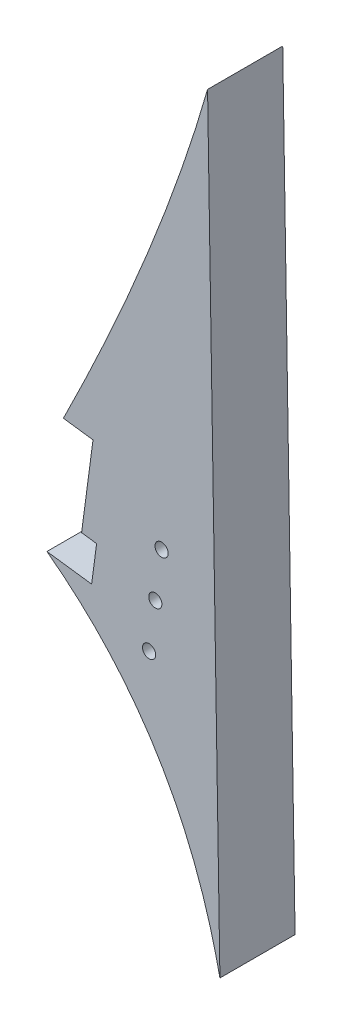
SolidWorks part; units mm, degrees
ref_plane "Front Plane" through (0, 0, 0) normal (0, 0, 1) x (1, 0, 0)
ref_plane "Top Plane" through (0, 0, 0) normal (0, 1, 0) x (1, 0, 0)
ref_plane "Right Plane" through (0, 0, 0) normal (1, 0, 0) x (0, 0, -1)
sketch "Sketch1" plane through (0, 0, 0) normal (0, 0, 1) x (1, 0, 0)
  line L0 (273.4348, -422.9361) -> (270.3947, -445.8352)
  line L1 (270.3947, -445.8352) -> (274.3947, -446.3662)
  line L3 (304.7874, -380.0704) -> (306.5247, -487.5803)
  line L6 (273.4348, -422.9361) -> (265.5529, -421.8897)
  line L8 (274.3947, -446.3662) -> (273.0671, -456.3662)
  line L9 (273.0671, -456.3662) -> (261.1715, -454.7869)
  line L10 (306.5247, -487.5803) -> (307.2114, -530.0766)
  line L13 (304.7874, -380.0704) -> (303.9283, -326.9032)
  spline S0 degree 2 poles (261.1715, -454.7869) (296.9639, -481.4674) (307.2114, -530.0766) knots 0 0 0 1 1 1
  spline S1 degree 2 poles (303.9283, -326.9032) (291.9193, -369.0267) (265.5529, -421.8897) knots 0 0 0 1 1 1
  dimension "D1" = 4
  dimension "D2" = 10
  dimension "D3" = 12
  dimension "D4" = 23.1
extrude "Boss-Extrude1" add sketch "Sketch1" along normal blind 20
sketch "Sketch2" plane through (0, 0, 20) normal (0, 0, 1) x (1, 0, 0)
  line L0 (288.3529, -464.1799) -> (291.6804, -439.1158) construction
  line L2 (273.4348, -422.9361) -> (270.3947, -445.8352) construction
  circle A0 centre (288.3529, -464.1799) radius 1.75
  circle A1 centre (290.0167, -451.6478) radius 1.75
  circle A2 centre (291.6804, -439.1158) radius 1.75
  dimension "D1" = 3.5
extrude "Cut-Extrude1" cut sketch "Sketch2" against normal through all
